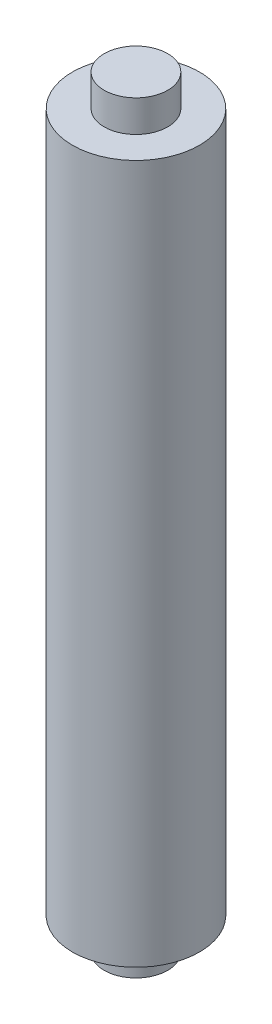
SolidWorks part; units mm, degrees
material "Cast Alloy Steel"
ref_plane "Front Plane" through (0, 0, 0) normal (0, 0, 1) x (1, 0, 0)
ref_plane "Top Plane" through (0, 0, 0) normal (0, 1, 0) x (1, 0, 0)
ref_plane "Right Plane" through (0, 0, 0) normal (1, 0, 0) x (0, 0, -1)
sketch "Sketch2" plane through (0, 0, 0) normal (0, 1, 0) x (1, 0, 0)
  circle A0 centre (0, 0) radius 5
  circle A1 centre (0, 0) radius 10
extrude "Boss-Extrude1" add sketch "Sketch2" along normal blind 110
extrude "Boss-Extrude2" add sketch "Sketch2<2>" along normal blind 115 contours A0 region at (0, 0, 0)
sketch "Sketch2<2>" plane through (0, 0, 0) normal (0, 1, 0) x (1, 0, 0) same geometry as "Sketch2"
extrude "Boss-Extrude3" add sketch "Sketch2<3>" against normal blind 5 contours A0 region at (0, 0, 0)
sketch "Sketch2<3>" plane through (0, 0, 0) normal (0, 1, 0) x (1, 0, 0) same geometry as "Sketch2"
